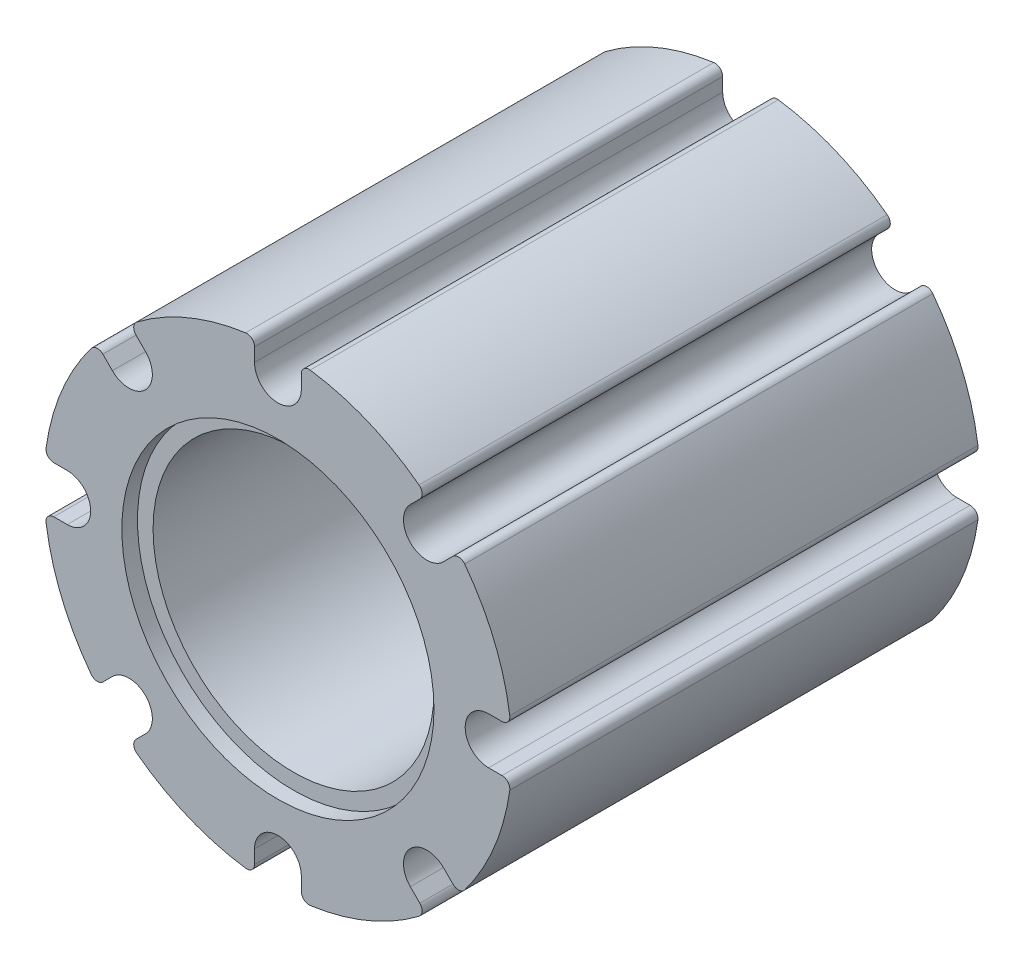
SolidWorks part; units mm, degrees
ref_plane "前视基准面" through (0, 0, 0) normal (0, 0, 1) x (1, 0, 0)
ref_plane "上视基准面" through (0, 0, 0) normal (0, 1, 0) x (1, 0, 0)
ref_plane "右视基准面" through (0, 0, 0) normal (1, 0, 0) x (0, 0, -1)
sketch "草图1" plane through (0, 0, 0) normal (0, 0, 1) x (1, 0, 0)
  line L0 (-22.9562, 0) -> (18.7081, 0) construction
  line L1 (-13.5, 1.5) -> (-14.9248, 1.5)
  line L2 (-13.5, -1.5) -> (-14.9248, -1.5)
  arc A0 (-14.9248, -1.5) -> (-14.9248, 1.5) centre (0, 0) ccw
  arc A1 (-13.5, -1.5) -> (-13.5, 1.5) centre (-13.5, 0) ccw
  circle A9 centre (0, 0) radius 2.5
  point P47 (0, 0)
  dimension "D1" = 3
  dimension "D2" = 30
  dimension "D4" = 5
extrude "凸台-拉伸1" add sketch "草图1" along normal blind 30
fillet "圆角1" radius 0.5 2 edges at (-14.9248, -1.5, 15) (-14.9248, 1.5, 15)
pattern_circular "阵列(圆周)3" count 8 over 360 about axis through (0, 0, 30) along (0, 0, -1) of face at (-13.9307, 1.5, 15) of face at (-12.75, 0, 15) of face at (-13.9307, -1.5, 15) of face at (-14.6738, 1.7281, 15) of face at (-14.6738, -1.7281, 15)
sketch "草图3" plane through (0, 0, 30) normal (0, 0, 1) x (1, 0, 0)
  circle A0 centre (0, 0) radius 10
  arc A1 (8.4853, 10.6066) -> (10.6066, 8.4853) centre (9.5459, 9.5459) ccw construction
  dimension "D1" = 20
  dimension "D2" = 2
extrude "切除-拉伸1" cut sketch "草图3" against normal blind 1
sketch "草图4" plane through (0, 0, 29) normal (0, 0, 1) x (1, 0, 0)
  circle A0 centre (0, 0) radius 9
  dimension "D1" = 18
extrude "切除-拉伸2" cut sketch "草图4" against normal blind 20
sketch "草图5" plane through (0, 0, 0) normal (0, 0, -1) x (-1, 0, 0)
  circle A0 centre (0, 0) radius 9
  dimension "D1" = 18
extrude "切除-拉伸3" cut sketch "草图5" against normal blind 0.5
sketch "草图2" plane through (0, 0, 0.5) normal (0, 0, -1) x (-1, 0, 0)
  circle A0 centre (0, 0) radius 3.5
  circle A1 centre (0, 0) radius 2.5 construction
  circle A2 centre (0, 0) radius 2.5
  dimension "D1" = 7
extrude "凸台-拉伸2" add sketch "草图2" along normal blind 1
chamfer "倒角1" distance 0.5 angle 45 1 edges at (2.5, 0, 9)
